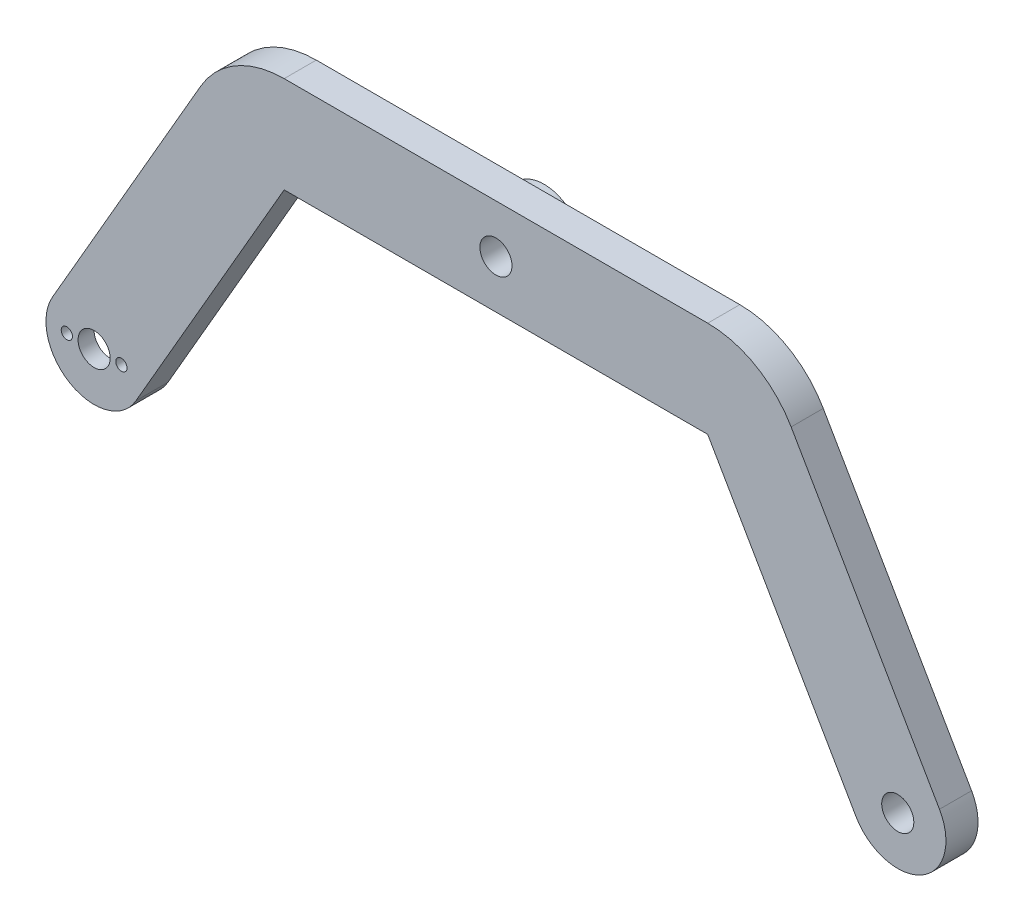
SolidWorks part; units mm, degrees
ref_plane "Front Plane" through (0, 0, 0) normal (0, 0, 1) x (1, 0, 0)
ref_plane "Top Plane" through (0, 0, 0) normal (0, 1, 0) x (1, 0, 0)
ref_plane "Right Plane" through (0, 0, 0) normal (1, 0, 0) x (0, 0, -1)
sketch "Sketch1" plane through (0, 0, 0) normal (0, 0, 1) x (1, 0, 0)
  line L0 (0, -15) -> (0, 15) construction
  line L1 (65.9559, 15) -> (-65.9559, 15)
  line L2 (65.9559, -15) -> (-65.9559, -15)
  line L3 (-65.9559, -15) -> (-112.1545, -95.0183)
  line L5 (-138.1353, -80.0183) -> (-91.9367, 0)
  line L6 (138.1353, -80.0183) -> (91.9367, 0)
  line L8 (65.9559, -15) -> (112.1545, -95.0183)
  arc A1 (-91.9367, 0) -> (-65.9559, 15) centre (-65.9559, -15) cw
  arc A2 (91.9367, 0) -> (65.9559, 15) centre (65.9559, -15) ccw
  circle A3 centre (-125.1449, -87.5183) radius 15 construction
  arc A5 (-138.1353, -80.0183) -> (-112.1545, -95.0183) centre (-125.1449, -87.5183) ccw
  arc A6 (112.1545, -95.0183) -> (138.1353, -80.0183) centre (125.1449, -87.5183) ccw
  circle A7 centre (-133.6449, -87.5183) radius 1.75
  circle A8 centre (-116.6449, -87.5183) radius 1.75
  point P4 (0, 0)
  point P6 (0, 15)
  point P10 (0, -15)
  dimension "D2" = 3.5
  dimension "D4" = 3.5
  dimension "D1" = 30
  dimension "D3" = 120
extrude "Boss-Extrude1" add sketch "Sketch1" along normal blind 10
sketch "Sketch2" plane through (0, 0, 10) normal (0, 0, 1) x (1, 0, 0)
  circle A0 centre (0, 0) radius 5
  circle A1 centre (-125.1449, -87.5183) radius 5
  circle A2 centre (125.1449, -87.5183) radius 5
extrude "Cut-Extrude1" cut sketch "Sketch2" against normal up to surface (10 mm away) up to face at (-131.8949, -87.5183, 0)
sketch "Sketch3" plane through (0, 0, 0) normal (0, 0, -1) x (-1, 0, 0)
  circle A0 centre (0, 0) radius 12
extrude "Boss-Extrude2" add sketch "Sketch3" along normal blind 5
sketch "Sketch4" plane through (0, 0, 0) normal (0, 0, -1) x (-1, 0, 0)
  circle A0 centre (125.1449, -87.5183) radius 13
  dimension "D1" = 26
extrude "Cut-Extrude2" cut sketch "Sketch4" against normal offset from surface (5 mm away) 5 up to face at (5, 0, 10)
